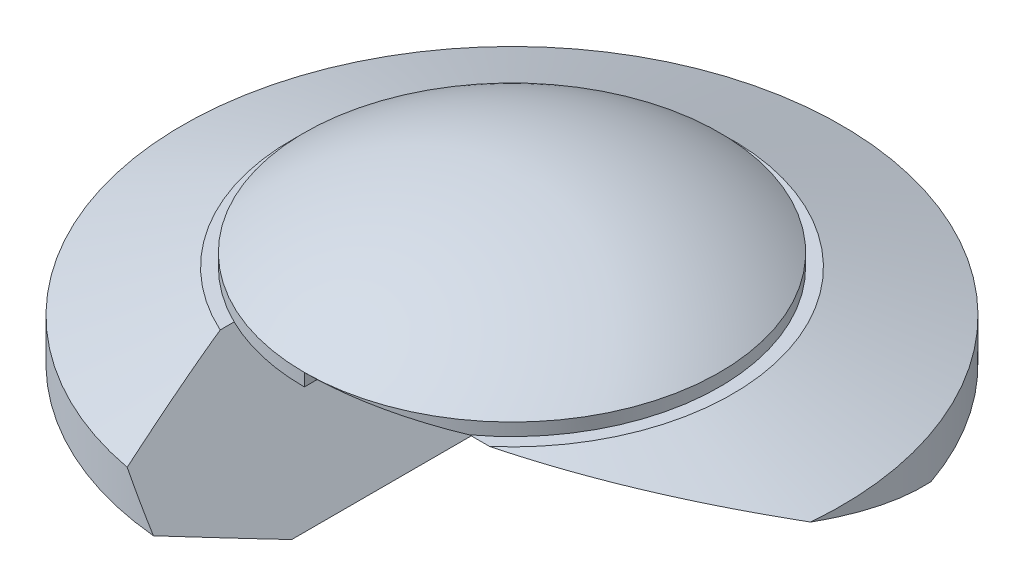
SolidWorks part; units mm, degrees
ref_plane "Alzado" through (0, 0, 0) normal (0, 0, 1) x (1, 0, 0)
ref_plane "Planta" through (0, 0, 0) normal (0, 1, 0) x (1, 0, 0)
ref_plane "Vista lateral" through (0, 0, 0) normal (1, 0, 0) x (0, 0, -1)
sketch "Croquis1" plane through (0, 0, 0) normal (0, 1, 0) x (1, 0, 0)
  circle A0 centre (0, 0) radius 52.5
  dimension "D1" = 105
extrude "Saliente-Extruir1" add sketch "Croquis1" along normal blind 10 draft 69 draft outward yes
sketch "Croquis2" plane through (0, 10, 0) normal (0, 1, 0) x (1, 0, 0)
  circle A0 centre (0, 0) radius 78.5509
  dimension "D1" = 157.1018
extrude "Saliente-Extruir2" add sketch "Croquis2" along normal blind 10
sketch "Croquis3" plane through (0, 20, 0) normal (0, 1, 0) x (1, 0, 0)
  circle A0 centre (0, 0) radius 78.5509
extrude "Saliente-Extruir3" add sketch "Croquis3" along normal blind 10 draft 69
sketch "Croquis4" plane through (0, 30, 0) normal (0, 1, 0) x (1, 0, 0)
  circle A0 centre (0, 0) radius 49.5
  dimension "D1" = 99
extrude "Saliente-Extruir4" add sketch "Croquis4" along normal blind 3
dome "Cúpula1" faces to dome 1 distance 16 reverse direction no elliptical dome no face at (0, 33, 49.5) parameters "D1"=16
sketch "Croquis6" plane through (0, 0, 0) normal (1, 0, 0) x (0, 0, -1)
  line L0 (-49.5, 33) -> (55.0644, 0.9844)
  line L1 (52.5, 0) -> (78.5509, 10) construction
  line L2 (-49.5, 33) -> (-78.5509, 20)
  line L3 (-78.5509, 20) -> (-78.5509, 10)
  line L4 (-78.5509, 10) -> (-52.5, 0)
  line L5 (-52.5, 0) -> (52.5, 0)
  line L6 (52.5, 0) -> (55.0644, 0.9844)
  dimension "D1" = 109.3559
extrude "Cortar-Extruir1" cut sketch "Croquis6" along normal through all
ref_plane "Plano1" through (0, 0, 78.5509) normal (0, 0, 1) x (1, 0, 0)
sketch "Croquis9" plane through (0, 0, 78.5509) normal (0, 0, 1) x (1, 0, 0)
  line L0 (0, 0) -> (-21.7963, 30)
  line L1 (52.5, 30) -> (-52.5, 30) construction
  line L2 (-21.7963, 30) -> (0, 30)
  line L3 (0, 30) -> (0, 0)
  line L4 (0, 0) -> (-17.4434, 0)
  line L5 (-52.5, 0) -> (0, 0) construction
  dimension "D1" = 54
extrude "Cortar-Extruir3" cut sketch "Croquis9" against normal up to surface (136.8303 mm away) contours L3 L0 L2 up to face at (36.8046, 20.5658, 8.8894)
ref_plane "Plano2" through (-49.5, 0, 0) normal (-1, 0, 0) x (0, 0, 1)
ref_plane "Plano3" through (0, 0, 20) normal (0, 0, 1) x (1, 0, 0)
ref_plane "Plano4" through (0, 0, -20) normal (0, 0, 1) x (1, 0, 0)
sketch "Croquis11" plane through (0, 0, 20) normal (0, 0, 1) x (1, 0, 0)
  line L0 (-41.36, 0) -> (-52.5, 0)
  line L1 (-52.5, 0) -> (0, 0) construction
  line L2 (-41.36, 0) -> (-59.9213, -15.5747)
  line L3 (-59.9213, -15.5747) -> (-77.9193, 5.8745)
  line L4 (-77.9193, 5.8745) -> (-78.5509, 5.3445)
  line L5 (-78.5509, 20) -> (-78.5509, 10) construction
  line L6 (-77.9193, 5.8745) -> (-63.3465, 16.2516)
  line L7 (-63.3465, 16.2516) -> (-52.5, 0)
  dimension "D1" = 40
  dimension "D2" = 11.14
  dimension "D3" = 24.23
  dimension "D4" = 28
  dimension "D5" = 17.89
extrude "Saliente-Extruir5" add sketch "Croquis11" along normal blind 6 contours L7 L6 L3 L2 L0 region at (-61.6643, 0.265, 20)
pattern_linear "MatrizL1" count 2 spacing 40 along (0, 0, -1) of "Saliente-Extruir5"
